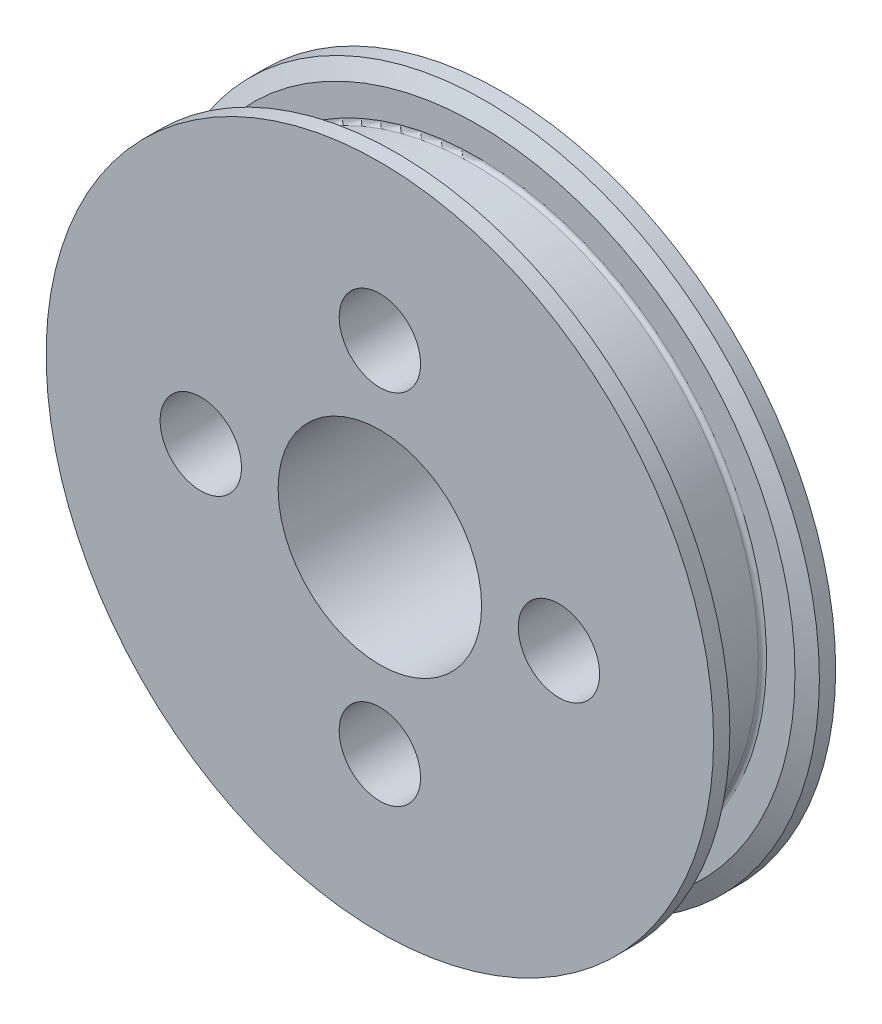
SolidWorks part; units mm, degrees
ref_plane "Front Plane" through (0, 0, 0) normal (0, 0, 1) x (1, 0, 0)
ref_plane "Top Plane" through (0, 0, 0) normal (0, 1, 0) x (1, 0, 0)
ref_plane "Right Plane" through (0, 0, 0) normal (1, 0, 0) x (0, 0, -1)
sketch "Sketch2" plane through (0, 0, 0) normal (1, 0, 0) x (0, 0, -1)
  line L0 (0, 6.35) -> (0, 20.828)
  line L1 (0, 20.828) -> (1.016, 20.828)
  line L2 (1.524, 19.812) -> (1.524, 17.78)
  line L3 (1.524, 17.78) -> (6.096, 17.78)
  line L4 (6.096, 17.78) -> (6.096, 19.812)
  line L5 (6.604, 20.828) -> (7.62, 20.828)
  line L6 (7.62, 20.828) -> (7.62, 6.35)
  line L8 (0, 6.35) -> (7.62, 6.35)
  line L9 (0, 6.35) -> (0, 0) construction
  line L10 (0, 0) -> (10.7816, 0) construction
  line L11 (6.096, 19.812) -> (6.604, 20.828)
  line L12 (1.016, 20.828) -> (1.524, 19.812)
  point P4 (1.524, 20.828)
  point P7 (6.096, 20.828)
  dimension "D1" = 17.78
  dimension "D2" = 7.62
  dimension "D3" = 3.048
  dimension "D4" = 6.35
  dimension "D5" = 4.572
  dimension "D6" = 1.016
  dimension "D7" = 0.508
  dimension "D8" = 0.508
  dimension "D9" = 1.016
revolve "Revolve1" add sketch "Sketch2" angle 360 about L10
sketch "Sketch3" plane through (0, 0, -7.62) normal (0, 0, -1) x (-1, 0, 0)
  line L1 (-8.255, -8.255) -> (8.255, -8.255)
  line L2 (-8.255, -8.255) -> (-8.255, 8.255)
  line L3 (-8.255, 8.255) -> (8.255, 8.255)
  line L4 (8.255, -8.255) -> (8.255, 8.255)
  circle A0 centre (0, 0) radius 6.35 construction
  circle A1 centre (0, 0) radius 6.35
  point P4 (8.255, 0)
  point P6 (0, 8.255)
  dimension "D1" = 16.51
extrude "Boss-Extrude1" add sketch "Sketch3" along normal blind 3.175
ref_plane "Plane1" through (0, 0, -3.81) normal (0, 0, -1) x (-1, 0, 0)
sketch "Sketch4" plane through (0, 0, -7.62) normal (0, 0, -1) x (-1, 0, 0)
  line L0 (0, 11.176) -> (0, 0) construction
  line L1 (0, 0) -> (0, -11.176) construction
  line L2 (-11.176, 0) -> (0, 0) construction
  line L3 (0, 0) -> (11.176, 0) construction
  circle A0 centre (0, 11.176) radius 2.54
  circle A1 centre (11.176, 0) radius 2.54
  circle A2 centre (0, -11.176) radius 2.54
  circle A3 centre (-11.176, 0) radius 2.54
  dimension "D1" = 5.08
  dimension "D2" = 11.176
extrude "Cut-Extrude1" cut sketch "Sketch4" against normal through all both and the other way through all
fillet "Fillet1" radius 0.254 2 edges at (17.78, 0, -6.096) (17.78, 0, -1.524)
